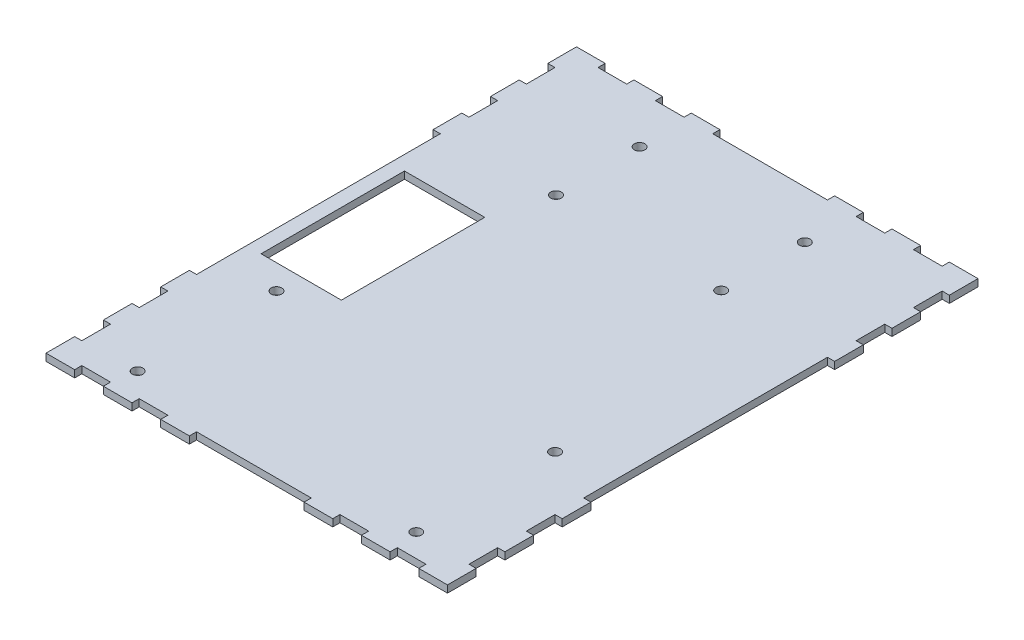
SolidWorks part; units mm, degrees
material "Acrylic (Medium-high impact)"
ref_plane "Front Plane" through (0, 0, 0) normal (0, 0, 1) x (1, 0, 0)
ref_plane "Top Plane" through (0, 0, 0) normal (0, 1, 0) x (1, 0, 0)
ref_plane "Right Plane" through (0, 0, 0) normal (1, 0, 0) x (0, 0, -1)
sketch "Sketch1" plane through (0, 0, 0) normal (0, 1, 0) x (1, 0, 0)
  line L0 (0, 209.55) -> (0, 196.85)
  line L1 (0, 0) -> (177.8, 0)
  line L2 (0, 0) -> (0, 234.95)
  line L3 (0, 234.95) -> (177.8, 234.95)
  line L4 (177.8, 0) -> (177.8, 234.95)
  line L5 (0, 234.95) -> (3.175, 234.95)
  line L6 (0, 234.95) -> (0, 0)
  line L7 (0, 0) -> (3.175, 0)
  line L8 (3.175, 234.95) -> (3.175, 0)
  line L9 (177.8, 234.95) -> (174.625, 234.95)
  line L10 (177.8, 234.95) -> (177.8, 0)
  line L11 (177.8, 0) -> (174.625, 0)
  line L12 (174.625, 234.95) -> (174.625, 0)
  line L13 (0, 234.95) -> (3.175, 234.95)
  line L14 (0, 234.95) -> (0, 222.25)
  line L15 (0, 222.25) -> (3.175, 222.25)
  line L16 (3.175, 234.95) -> (3.175, 222.25)
  line L17 (0, 209.55) -> (3.175, 209.55)
  line L18 (3.175, 209.55) -> (3.175, 196.85)
  line L19 (0, 196.85) -> (3.175, 196.85)
  line L20 (0, 184.15) -> (0, 171.45)
  line L21 (0, 184.15) -> (3.175, 184.15)
  line L22 (3.175, 184.15) -> (3.175, 171.45)
  line L23 (0, 171.45) -> (3.175, 171.45)
  line L24 (0, 117.475) -> (177.8, 117.475) construction
  line L25 (88.9, 234.95) -> (88.9, 0) construction
  line L26 (177.8, 171.45) -> (174.625, 171.45)
  line L27 (174.625, 184.15) -> (174.625, 171.45)
  line L28 (177.8, 184.15) -> (174.625, 184.15)
  line L29 (177.8, 184.15) -> (177.8, 171.45)
  line L30 (177.8, 196.85) -> (174.625, 196.85)
  line L31 (174.625, 209.55) -> (174.625, 196.85)
  line L32 (177.8, 209.55) -> (174.625, 209.55)
  line L33 (174.625, 234.95) -> (174.625, 222.25)
  line L34 (177.8, 222.25) -> (174.625, 222.25)
  line L35 (177.8, 234.95) -> (177.8, 222.25)
  line L36 (177.8, 234.95) -> (174.625, 234.95)
  line L37 (177.8, 234.95) -> (177.8, 0)
  line L38 (177.8, 234.95) -> (174.625, 234.95)
  line L39 (177.8, 209.55) -> (177.8, 196.85)
  line L40 (177.8, 25.4) -> (177.8, 38.1)
  line L41 (177.8, 0) -> (174.625, 0)
  line L42 (177.8, 0) -> (174.625, 0)
  line L43 (177.8, 0) -> (177.8, 12.7)
  line L44 (177.8, 12.7) -> (174.625, 12.7)
  line L45 (174.625, 0) -> (174.625, 12.7)
  line L46 (177.8, 25.4) -> (174.625, 25.4)
  line L47 (174.625, 25.4) -> (174.625, 38.1)
  line L48 (177.8, 38.1) -> (174.625, 38.1)
  line L49 (177.8, 50.8) -> (177.8, 63.5)
  line L50 (177.8, 50.8) -> (174.625, 50.8)
  line L51 (174.625, 50.8) -> (174.625, 63.5)
  line L52 (177.8, 63.5) -> (174.625, 63.5)
  line L53 (0, 63.5) -> (3.175, 63.5)
  line L54 (3.175, 50.8) -> (3.175, 63.5)
  line L55 (0, 50.8) -> (3.175, 50.8)
  line L56 (0, 50.8) -> (0, 63.5)
  line L57 (0, 38.1) -> (3.175, 38.1)
  line L58 (3.175, 25.4) -> (3.175, 38.1)
  line L59 (0, 25.4) -> (3.175, 25.4)
  line L60 (3.175, 0) -> (3.175, 12.7)
  line L61 (0, 12.7) -> (3.175, 12.7)
  line L62 (0, 0) -> (0, 12.7)
  line L63 (0, 0) -> (3.175, 0)
  line L64 (177.8, 0) -> (174.625, 0)
  line L65 (0, 0) -> (3.175, 0)
  line L66 (0, 0) -> (177.8, 0)
  line L67 (0, 25.4) -> (0, 38.1)
  dimension "D1" = 234.95
  dimension "D2" = 177.8
  dimension "D3" = 3.175
  dimension "D4" = 3.175
  dimension "D5" = 12.7
  dimension "D6" = 3.175
  dimension "D7" = 3
extrude "Boss-Extrude1" add sketch "Sketch1" along normal blind 3.175 contours L6 L55 L8 L53 | L6 L59 L8 L57 | L61 L2 L1 L8 | L6 L23 L8 L21 | L0 L19 L8 L17 | L6 L15 L8 L3 | L4 L44 L12 L1 | L37 L48 L12 L46 | L37 L52 L12 L50 | L34 L10 L3 L12 | L10 L32 L12 L30 | L10 L28 L12 L26 | L52 L12 L26 L27 L28 L30 L31 L32 L34 L33 L3 L8 L1 L45 L44 L46 L47 L48 L50 L51 region at (1.5875, 0, -203.2) region at (1.5875, 0, -228.6) region at (88.9, 0, -117.475) region at (1.5875, 0, -177.8) region at (1.5875, 0, -57.15) region at (176.2125, 0, -228.6) region at (1.5875, 0, -31.75) region at (176.2125, 0, -203.2) region at (1.5875, 0, -6.35) region at (176.2125, 0, -177.8) region at (176.2125, 0, -57.15) region at (176.2125, 0, -6.35) region at (176.2125, 0, -31.75)
sketch "Sketch5" plane through (0, 3.175, 0) normal (0, 1, 0) x (1, 0, 0)
  line L0 (88.9, 0) -> (88.9, 18.3402) construction
  line L1 (0, 0) -> (177.8, 0) construction
  line L3 (0, 0) -> (12.7, 0)
  line L4 (0, 0) -> (0, 3.175)
  line L5 (0, 3.175) -> (12.7, 3.175)
  line L6 (12.7, 0) -> (12.7, 3.175)
  line L10 (25.4, 3.175) -> (38.1, 3.175)
  line L11 (25.4, 0) -> (38.1, 0)
  line L12 (38.1, 0) -> (38.1, 3.175)
  line L13 (25.4, 0) -> (25.4, 3.175)
  line L14 (50.8, 3.175) -> (63.5, 3.175)
  line L15 (50.8, 0) -> (63.5, 0)
  line L16 (63.5, 0) -> (63.5, 3.175)
  line L17 (50.8, 0) -> (50.8, 3.175)
  line L18 (0, 3.175) -> (177.8, 3.175)
  line L19 (127, 0) -> (127, 3.175)
  line L20 (114.3, 0) -> (114.3, 3.175)
  line L21 (127, 0) -> (114.3, 0)
  line L22 (127, 3.175) -> (114.3, 3.175)
  line L23 (152.4, 0) -> (152.4, 3.175)
  line L24 (139.7, 0) -> (139.7, 3.175)
  line L25 (152.4, 0) -> (139.7, 0)
  line L26 (152.4, 3.175) -> (139.7, 3.175)
  line L27 (165.1, 0) -> (165.1, 3.175)
  line L28 (177.8, 3.175) -> (165.1, 3.175)
  line L29 (177.8, 0) -> (177.8, 3.175)
  line L30 (177.8, 0) -> (165.1, 0)
  line L63 (0, 63.5) -> (0, 50.8)
  line L64 (0, 50.8) -> (3.175, 50.8)
  line L65 (3.175, 50.8) -> (3.175, 38.1)
  line L66 (3.175, 38.1) -> (0, 38.1)
  line L67 (0, 38.1) -> (0, 25.4)
  line L68 (0, 25.4) -> (3.175, 25.4)
  line L69 (3.175, 25.4) -> (3.175, 12.7)
  line L70 (3.175, 12.7) -> (0, 12.7)
  line L71 (0, 12.7) -> (0, 0)
  line L72 (0, 0) -> (177.8, 0)
  line L73 (177.8, 0) -> (177.8, 12.7)
  line L74 (177.8, 12.7) -> (174.625, 12.7)
  line L75 (174.625, 12.7) -> (174.625, 25.4)
  line L76 (174.625, 25.4) -> (177.8, 25.4)
  line L77 (177.8, 25.4) -> (177.8, 38.1)
  line L78 (177.8, 38.1) -> (174.625, 38.1)
  line L79 (174.625, 38.1) -> (174.625, 50.8)
  line L80 (174.625, 50.8) -> (177.8, 50.8)
  line L81 (177.8, 50.8) -> (177.8, 63.5)
  line L82 (177.8, 63.5) -> (174.625, 63.5)
  line L83 (174.625, 63.5) -> (174.625, 171.45)
  line L84 (174.625, 171.45) -> (177.8, 171.45)
  line L85 (177.8, 171.45) -> (177.8, 184.15)
  line L86 (177.8, 184.15) -> (174.625, 184.15)
  line L87 (174.625, 184.15) -> (174.625, 196.85)
  line L88 (174.625, 196.85) -> (177.8, 196.85)
  line L89 (177.8, 196.85) -> (177.8, 209.55)
  line L90 (177.8, 209.55) -> (174.625, 209.55)
  line L91 (174.625, 209.55) -> (174.625, 222.25)
  line L92 (174.625, 222.25) -> (177.8, 222.25)
  line L93 (177.8, 222.25) -> (177.8, 234.95)
  line L94 (177.8, 234.95) -> (0, 234.95)
  line L95 (0, 234.95) -> (0, 222.25)
  line L96 (0, 222.25) -> (3.175, 222.25)
  line L97 (3.175, 222.25) -> (3.175, 209.55)
  line L98 (3.175, 209.55) -> (0, 209.55)
  line L99 (0, 209.55) -> (0, 196.85)
  line L100 (0, 196.85) -> (3.175, 196.85)
  line L101 (3.175, 196.85) -> (3.175, 184.15)
  line L102 (3.175, 184.15) -> (0, 184.15)
  line L103 (0, 184.15) -> (0, 171.45)
  line L104 (0, 171.45) -> (3.175, 171.45)
  line L105 (3.175, 171.45) -> (3.175, 63.5)
  line L106 (3.175, 63.5) -> (0, 63.5)
  line L107 (0, 63.5) -> (0, 50.8)
  line L108 (0, 50.8) -> (3.175, 50.8)
  line L109 (3.175, 50.8) -> (3.175, 38.1)
  line L110 (3.175, 38.1) -> (0, 38.1)
  line L111 (0, 38.1) -> (0, 25.4)
  line L112 (0, 25.4) -> (3.175, 25.4)
  line L113 (3.175, 25.4) -> (3.175, 12.7)
  line L114 (3.175, 12.7) -> (0, 12.7)
  line L115 (0, 12.7) -> (0, 0)
  line L116 (0, 0) -> (177.8, 0)
  line L117 (177.8, 0) -> (177.8, 12.7)
  line L118 (177.8, 12.7) -> (174.625, 12.7)
  line L119 (174.625, 12.7) -> (174.625, 25.4)
  line L120 (174.625, 25.4) -> (177.8, 25.4)
  line L121 (177.8, 25.4) -> (177.8, 38.1)
  line L122 (177.8, 38.1) -> (174.625, 38.1)
  line L123 (174.625, 38.1) -> (174.625, 50.8)
  line L124 (174.625, 50.8) -> (177.8, 50.8)
  line L125 (177.8, 50.8) -> (177.8, 63.5)
  line L126 (177.8, 63.5) -> (174.625, 63.5)
  line L127 (174.625, 63.5) -> (174.625, 171.45)
  line L128 (174.625, 171.45) -> (177.8, 171.45)
  line L129 (177.8, 171.45) -> (177.8, 184.15)
  line L130 (177.8, 184.15) -> (174.625, 184.15)
  line L131 (174.625, 184.15) -> (174.625, 196.85)
  line L132 (174.625, 196.85) -> (177.8, 196.85)
  line L133 (177.8, 196.85) -> (177.8, 209.55)
  line L134 (177.8, 209.55) -> (174.625, 209.55)
  line L135 (174.625, 209.55) -> (174.625, 222.25)
  line L136 (174.625, 222.25) -> (177.8, 222.25)
  line L137 (177.8, 222.25) -> (177.8, 234.95)
  line L138 (177.8, 234.95) -> (0, 234.95)
  line L139 (0, 234.95) -> (0, 222.25)
  line L140 (0, 222.25) -> (3.175, 222.25)
  line L141 (3.175, 222.25) -> (3.175, 209.55)
  line L142 (3.175, 209.55) -> (0, 209.55)
  line L143 (0, 209.55) -> (0, 196.85)
  line L144 (0, 196.85) -> (3.175, 196.85)
  line L145 (3.175, 196.85) -> (3.175, 184.15)
  line L146 (3.175, 184.15) -> (0, 184.15)
  line L147 (0, 184.15) -> (0, 171.45)
  line L148 (0, 171.45) -> (3.175, 171.45)
  line L149 (3.175, 171.45) -> (3.175, 63.5)
  line L150 (3.175, 63.5) -> (0, 63.5)
  point P22 (88.9, 3.175)
  dimension "D1" = 3.175
  dimension "D2" = 12.7
  dimension "D4" = 0
  dimension "D3" = 3
extrude "Cut-Extrude4" cut sketch "Sketch5" against normal blind 7.62 contours L6 L116 L13 L18 | L12 L116 L17 L18 | L116 L0 L18 L16 | L0 L116 L20 L18 | L19 L116 L24 L18 | L23 L116 L27 L18 region at (76.2, 3.175, -1.5875) region at (101.6, 3.175, -1.5875) region at (44.45, 3.175, -1.5875) region at (133.35, 3.175, -1.5875) region at (19.05, 3.175, -1.5875) region at (158.75, 3.175, -1.5875)
ref_plane "Plane2" through (0, 0, -117.475) normal (0, 0, 1) x (1, 0, 0)
mirror "Mirror1" about plane through (0, 0, -117.475) normal (0, 0, 1) of "Cut-Extrude4"
sketch "Sketch7" plane through (0, 3.175, 0) normal (0, 1, 0) x (1, 0, 0)
  line L0 (3.175, 117.475) -> (174.625, 117.475) construction
  line L1 (3.175, 171.45) -> (3.175, 63.5) construction
  line L2 (174.625, 171.45) -> (174.625, 63.5) construction
  line L3 (3.175, 117.475) -> (9.525, 117.475) construction
  line L4 (9.525, 117.475) -> (9.525, 149.225)
  line L6 (9.525, 149.225) -> (45.085, 149.225)
  line L7 (9.525, 149.225) -> (9.525, 85.725)
  line L8 (9.525, 85.725) -> (45.085, 85.725)
  line L9 (45.085, 149.225) -> (45.085, 85.725)
  dimension "D1" = 6.35
  dimension "D2" = 31.75
  dimension "D3" = 63.5
  dimension "D4" = 35.56
extrude "Cut-Extrude5" cut sketch "Sketch7" against normal blind 7.62 contours L6 L9 L8 L7
sketch "Sketch8" plane through (0, 3.175, 0) normal (0, 1, 0) x (1, 0, 0)
  line L1 (0, 0) -> (27.2089, 0)
  line L2 (0, 0) -> (0, 13.3771)
  line L3 (0, 13.3771) -> (27.2089, 13.3771)
  line L4 (27.2089, 0) -> (27.2089, 13.3771)
  line L5 (27.2089, 13.3771) -> (150.5911, 13.3771)
  line L6 (27.2089, 13.3771) -> (27.2089, 74.8494)
  line L7 (27.2089, 74.8494) -> (150.5911, 74.8494)
  line L8 (150.5911, 13.3771) -> (150.5911, 74.8494)
  circle A0 centre (27.2089, 74.8494) radius 2.3495
  circle A1 centre (27.2089, 13.3771) radius 2.3495
  circle A2 centre (150.5911, 74.8494) radius 2.3495
  circle A3 centre (150.5911, 13.3771) radius 2.3495
  dimension "D5" = 4.699
  dimension "D6" = 4.699
  dimension "D7" = 4.699
  dimension "D8" = 4.699
  dimension "D1" = 27.2089
  dimension "D2" = 13.3771
  dimension "D3" = 123.3821
  dimension "D4" = 61.4723
extrude "Cut-Extrude6" cut sketch "Sketch8" against normal blind 7.62 contours L3 A1 L4 | L6 A1 L3 | L5 A1 L6 | L4 A1 L5 | L6 A0 L7 | L7 A0 L6 | L7 A2 L8 | L8 A2 L7 | L8 A3 L5 | L5 A3 L8 region at (26.2118, 3.175, -12.3799) region at (28.2061, 3.175, -12.3799) region at (26.2118, 3.175, -14.3742) region at (28.2061, 3.175, -14.3742) region at (149.5939, 3.175, -14.3742) region at (150.9234, 3.175, -13.0447) region at (26.8766, 3.175, -75.1817) region at (28.2061, 3.175, -73.8522) region at (149.5939, 3.175, -73.8522) region at (150.9234, 3.175, -75.1817)
sketch "Sketch9" plane through (0, 3.175, 0) normal (0, 1, 0) x (1, 0, 0)
  line L0 (-5.2862, 234.95) -> (-5.2862, 210.5603) construction
  line L2 (-5.2862, 210.5603) -> (188.1579, 210.5603) construction
  line L3 (0, 177.8) -> (52.3212, 177.8) construction
  line L4 (0, 171.45) -> (0, 184.15) construction
  line L5 (52.3212, 177.8) -> (52.3212, 234.95) construction
  line L6 (50.8, 234.95) -> (63.5, 234.95) construction
  line L7 (88.9, 231.775) -> (88.9, 217.0356) construction
  line L8 (63.5, 231.775) -> (114.3, 231.775) construction
  line L9 (0, 234.95) -> (12.7, 234.95) construction
  line L10 (-5.2862, 210.5603) -> (-5.2862, 173.5457) construction
  line L11 (-5.2862, 173.5457) -> (186.199, 173.5457) construction
  line L12 (52.3212, 177.8) -> (52.3212, 173.5457) construction
  line L13 (52.3212, 173.5457) -> (52.3212, 210.5603) construction
  circle A0 centre (52.3212, 210.5603) radius 2.3495
  circle A1 centre (52.3212, 173.5457) radius 2.3495
  circle A2 centre (125.4788, 173.5457) radius 2.3495
  circle A3 centre (125.4788, 210.5603) radius 2.3495
  dimension "D4" = 4.699
  dimension "D5" = 4.699
  dimension "D1" = 24.3897
  dimension "D2" = 52.3212
  dimension "D3" = 37.0146
extrude "Cut-Extrude7" cut sketch "Sketch9" against normal blind 25.4
